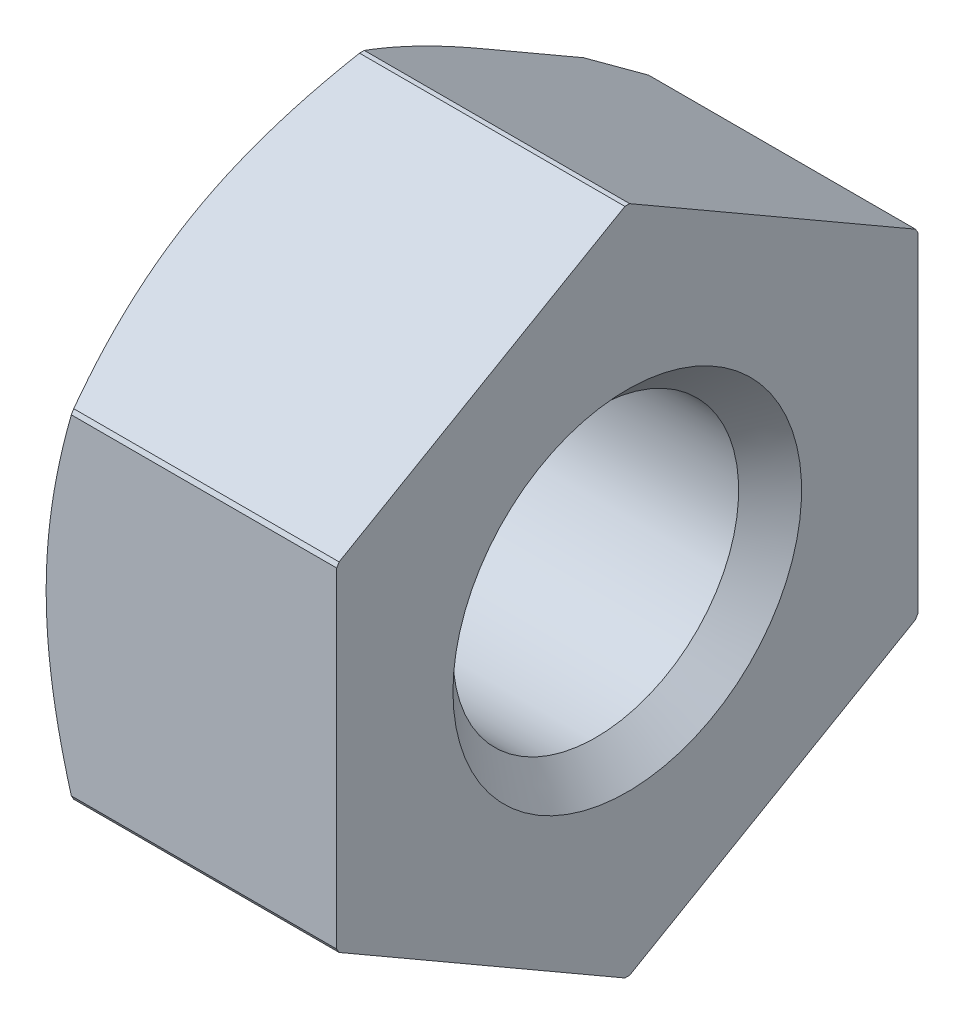
SolidWorks part; units mm, degrees
ref_plane "Front Plane" through (0, 0, 0) normal (0, 0, 1) x (1, 0, 0)
ref_plane "Top Plane" through (0, 0, 0) normal (0, 1, 0) x (1, 0, 0)
ref_plane "Right Plane" through (0, 0, 0) normal (1, 0, 0) x (0, 0, -1)
ref_plane "Plane1" through (-2.5, 0, 0) normal (-1, 0, 0) x (0, -1, 0)
sketch "Sketch1" plane through (-2.5, 0, 0) normal (-1, 0, 0) x (0, -1, 0)
  line L0 (5.7499, 0.041) -> (2.9104, 4.959)
  line L1 (2.8395, 5) -> (-2.8395, 5)
  line L2 (-2.9104, 4.959) -> (-5.7499, 0.041)
  line L3 (-5.7499, -0.041) -> (-2.9104, -4.959)
  line L4 (-2.8395, -5) -> (2.8395, -5)
  line L5 (2.9104, -4.959) -> (5.7499, -0.041)
  arc A0 (2.9104, 4.959) -> (2.8395, 5) centre (0, 0) ccw
  arc A1 (-2.8395, 5) -> (-2.9104, 4.959) centre (0, 0) ccw
  arc A2 (-5.7499, 0.041) -> (-5.7499, -0.041) centre (0, 0) ccw
  arc A3 (-2.9104, -4.959) -> (-2.8395, -5) centre (0, 0) ccw
  arc A4 (2.8395, -5) -> (2.9104, -4.959) centre (0, 0) ccw
  arc A5 (5.7499, -0.041) -> (5.7499, 0.041) centre (0, 0) ccw
extrude "Boss-Extrude1" add sketch "Sketch1" against normal blind 5
hole_wizard "Hole1" positions "Sketch3" profile "Sketch2" legacy
sketch "Sketch3" plane through (-2.5, 0, 0) normal (-1, 0, 0) x (0, 0, 1)
  point P0 (0, 0)
sketch "Sketch2" plane through (-2.5, 0, 0) normal (0, 1, 0) x (0, 0, 1)
  line L0 (0, 0) -> (0, 5)
  line L1 (0, 5) -> (2.4585, 5)
  line L2 (2.4585, 5) -> (2.4585, 0)
  line L3 (2.4585, 0) -> (0, 0)
  line L4 (0, 110) -> (0, -10) construction
  dimension "Diameter" = 4.917
  dimension "Depth" = 5
chamfer "Chamfer1" distance 0.75 angle 30 6 edges at (-2.5, -5.75, 0) (-2.5, 5.75, 0) (-2.5, 0, -5) (-2.5, -2.875, -4.9796) (-2.5, 2.875, 4.9796) (-2.5, -2.875, 4.9796) first distance on face at (-2.5, 0, 2.4585)
chamfer "Chamfer2" distance 0.5415 angle 45 2 edges at (2.5, 0, 2.4585) (-2.5, 0, 2.4585)
